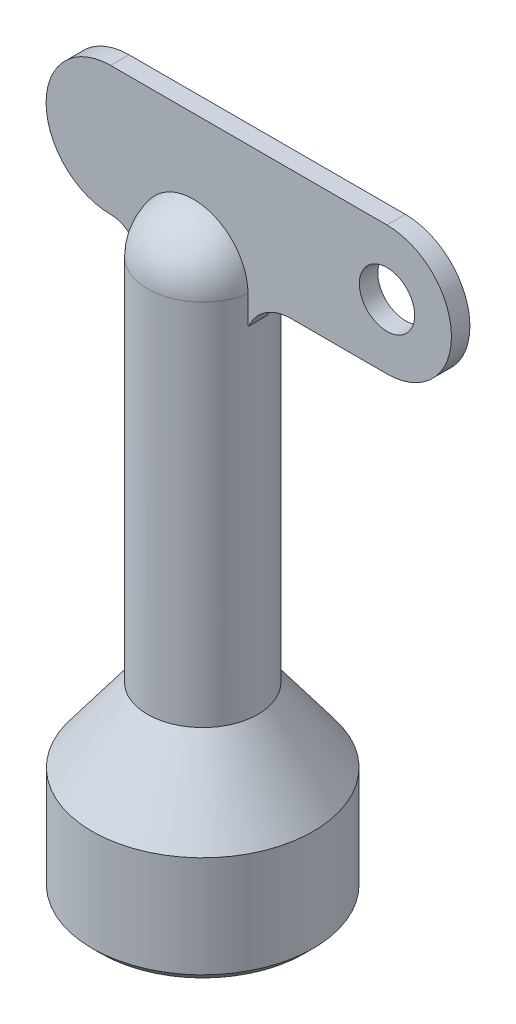
SolidWorks part; units mm, degrees
ref_plane "前视基准面" through (0, 0, 0) normal (0, 0, 1) x (1, 0, 0)
ref_plane "上视基准面" through (0, 0, 0) normal (0, 1, 0) x (1, 0, 0)
ref_plane "右视基准面" through (0, 0, 0) normal (1, 0, 0) x (0, 0, -1)
sketch "草图1" plane through (0, 0, 0) normal (0, 1, 0) x (1, 0, 0)
  circle A0 centre (0, 0) radius 6
  dimension "D1" = 12
extrude "凸台-拉伸1" add sketch "草图1" against normal blind 6
ref_plane "基准面1" through (0, 4, 0) normal (0, 1, 0) x (1, 0, 0)
sketch "草图2" plane through (0, 4, 0) normal (0, 1, 0) x (1, 0, 0)
  circle A0 centre (0, 0) radius 3
  dimension "D1" = 6
loft "放样1" add profiles "草图2", "草图1<2>" connector at (-2.9998, 4, -0.0339) connector at (-6, 0, 0)
sketch "草图1<2>" plane through (0, 0, 0) normal (0, 1, 0) x (1, 0, 0) same geometry as "草图1"
extrude "凸台-拉伸2" add sketch "草图2<2>" along normal blind 20
sketch "草图2<2>" plane through (0, 4, 0) normal (0, 1, 0) x (1, 0, 0) same geometry as "草图2"
sketch "草图7" plane through (0, 0, 0) normal (0, 0, 1) x (1, 0, 0)
  line L0 (0, 0) -> (0, 34.6838) construction
  line L1 (0, -6) -> (0, 0) construction
  line L2 (0, 24) -> (0, 4) construction
  line L3 (-3, 24) -> (-3, 4) construction
  line L4 (3, 4) -> (3, 24) construction
  line L5 (-3, 24) -> (0, 24)
  line L6 (0, 24) -> (0, 27)
  arc A0 (-3, 24) -> (0, 27) centre (0, 24) cw
revolve "旋转2" add sketch "草图7" angle 360 about L0
sketch "草图5" plane through (0, 0, 0) normal (0, 0, 1) x (1, 0, 0)
  line L0 (-3, 22.5) -> (3, 22.5)
  line L1 (5.2913, 24) -> (10.5, 24)
  line L2 (3, 4) -> (3, 24) construction
  line L3 (10.5, 31) -> (-4.5, 31)
  line L4 (3, 24) -> (-3, 24) construction
  line L6 (-3, 24) -> (-3, 4) construction
  arc A0 (-4.5, 31) -> (-4.5, 24) centre (-4.5, 27.5) ccw
  arc A1 (10.5, 31) -> (10.5, 24) centre (10.5, 27.5) cw
  arc A2 (-3, 22.5) -> (-4.5, 24) centre (-4.5, 22.5) ccw
  arc A3 (5.2913, 24) -> (3, 22.5) centre (5.2913, 21.5) ccw
  point P10 (-8, 27.5)
  dimension "D4" = 3
  dimension "D5" = 2.5
  dimension "D1" = 7
  dimension "D2" = 15
  dimension "D3" = 5
extrude "凸台-拉伸4" add sketch "草图5" along normal mid plane 1
sketch "草图8" plane through (0, 0, 0.5) normal (0, 0, 1) x (1, 0, 0)
  circle A0 centre (10.5, 27.5) radius 1.5
  dimension "D1" = 3
extrude "切除-拉伸1" cut sketch "草图8" against normal through all
sketch "草图9" plane through (0, -6, 0) normal (0, -1, 0) x (1, 0, 0)
  line L0 (0, 0) -> (6.3177, 0) construction
  line L1 (-0.1732, 4.7) -> (-4.1569, -2.2)
  line L2 (-3.9837, -2.5) -> (3.9837, -2.5)
  line L3 (4.1569, -2.2) -> (0.1732, 4.7)
  line L4 (3.9837, -2.3) -> (0, 0) construction
  circle A0 centre (0, 0) radius 5 construction
  arc A1 (4.1569, -2.2) -> (3.9837, -2.5) centre (3.9837, -2.3) cw
  arc A2 (-3.9837, -2.5) -> (-4.1569, -2.2) centre (-3.9837, -2.3) cw
  arc A3 (0.1732, 4.7) -> (-0.1732, 4.7) centre (0, 4.6) ccw
  point P12 (0, 5)
  dimension "D1" = 10
  dimension "D2" = 0.2
  dimension "D3" = 30
extrude "切除-拉伸2" cut sketch "草图9" against normal blind 5
chamfer "倒角1" distance 0.5 angle 30 6 edges at (0, -6, -2.5) (2.1651, -6, 1.25) (4.1569, -6, -2.4) (0, -6, 4.8) (-4.1569, -6, -2.4) (-2.1651, -6, 1.25) first distance on face at (0, -6, 0)
chamfer "倒角2" distance 0.5 angle 45 1 edges at (0, -6, 6)
